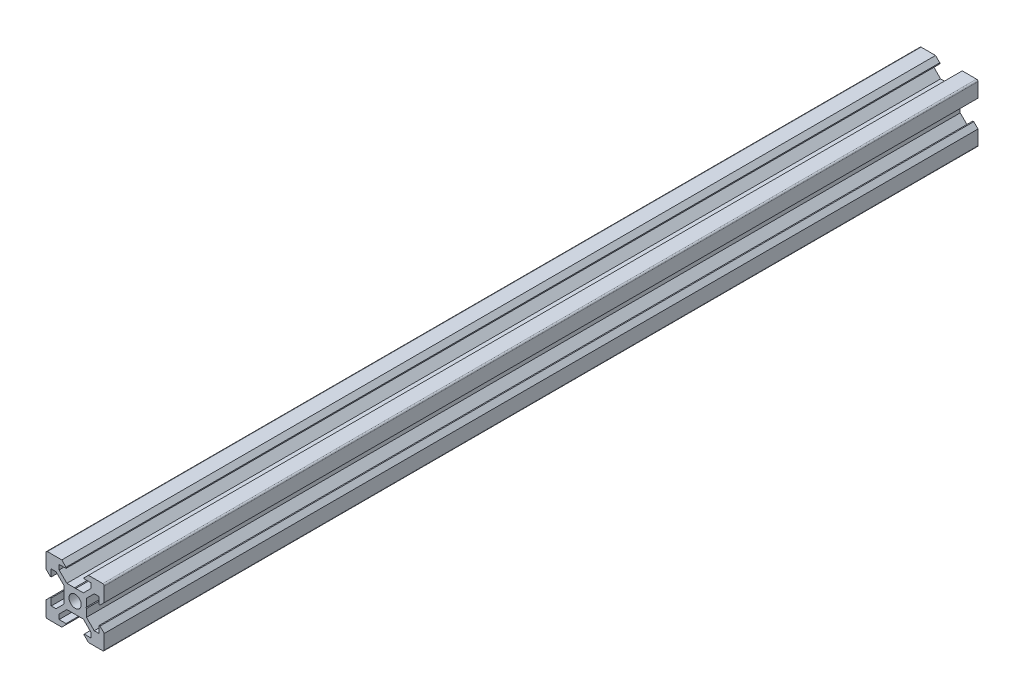
SolidWorks part; units mm, degrees
material "6061-T6 (SS)"
ref_plane "Front Plane" through (0, 0, 0) normal (0, 0, 1) x (1, 0, 0)
ref_plane "Top Plane" through (0, 0, 0) normal (0, 1, 0) x (1, 0, 0)
ref_plane "Right Plane" through (0, 0, 0) normal (1, 0, 0) x (0, 0, -1)
sketch "Sketch1" plane through (0, 0, 0) normal (0, 0, 1) x (1, 0, 0)
  line L1 (9.5, -10) -> (-9.5, -10)
  line L2 (10, -9.5) -> (10, 9.5)
  line L3 (9.5, 10) -> (-9.5, 10)
  line L4 (-10, -9.5) -> (-10, 9.5)
  line L5 (10, -10) -> (-10, 10) construction
  line L6 (10, 10) -> (-10, -10) construction
  circle A0 centre (0, 0) radius 2.1
  arc A1 (-9.5, 10) -> (-10, 9.5) centre (-9.5, 9.5) ccw
  arc A2 (10, 9.5) -> (9.5, 10) centre (9.5, 9.5) ccw
  arc A3 (9.5, -10) -> (10, -9.5) centre (9.5, -9.5) ccw
  arc A4 (-9.5, -10) -> (-10, -9.5) centre (-9.5, -9.5) cw
  point P0 (0, 0)
  line B0 (0, 0) -> (0, 10) construction
  line B1 (0, 3.69) -> (-0.21, 3.9)
  line B2 (-0.21, 3.9) -> (-2.8393, 3.9)
  line B3 (-2.8393, 3.9) -> (-5.5, 6.5607)
  line B4 (-5.5, 6.5607) -> (-5.5, 8.2)
  line B5 (-5.5, 8.2) -> (-3.125, 8.2)
  line B6 (-3.125, 8.2) -> (-3.125, 8.545)
  line B7 (-3.125, 8.545) -> (-4.58, 10)
  line B8 (-4.58, 10) -> (4.58, 10)
  line B9 (0, 0) -> (-5.9132, 5.9132) construction
  line B10 (3.125, 8.545) -> (4.58, 10)
  line B11 (3.125, 8.2) -> (3.125, 8.545)
  line B12 (5.5, 8.2) -> (3.125, 8.2)
  line B13 (5.5, 6.5607) -> (5.5, 8.2)
  line B14 (2.8393, 3.9) -> (5.5, 6.5607)
  line B15 (0.21, 3.9) -> (2.8393, 3.9)
  line B16 (0, 3.69) -> (0.21, 3.9)
  line B17 (0, 0) -> (-10, 0) construction
  line B18 (-3.69, 0) -> (-3.9, -0.21)
  line B19 (-3.9, -0.21) -> (-3.9, -2.8393)
  line B20 (-3.9, -2.8393) -> (-6.5607, -5.5)
  line B21 (-6.5607, -5.5) -> (-8.2, -5.5)
  line B22 (-8.2, -5.5) -> (-8.2, -3.125)
  line B23 (-8.2, -3.125) -> (-8.545, -3.125)
  line B24 (-8.545, -3.125) -> (-10, -4.58)
  line B25 (-10, -4.58) -> (-10, 4.58)
  line B26 (0, 0) -> (-5.9132, -5.9132) construction
  line B27 (-8.545, 3.125) -> (-10, 4.58)
  line B28 (-8.2, 3.125) -> (-8.545, 3.125)
  line B29 (-8.2, 5.5) -> (-8.2, 3.125)
  line B30 (-6.5607, 5.5) -> (-8.2, 5.5)
  line B31 (-3.9, 2.8393) -> (-6.5607, 5.5)
  line B32 (-3.9, 0.21) -> (-3.9, 2.8393)
  line B33 (-3.69, 0) -> (-3.9, 0.21)
  line B34 (0, 0) -> (0, -10) construction
  line B35 (0, -3.69) -> (0.21, -3.9)
  line B36 (0.21, -3.9) -> (2.8393, -3.9)
  line B37 (2.8393, -3.9) -> (5.5, -6.5607)
  line B38 (5.5, -6.5607) -> (5.5, -8.2)
  line B39 (5.5, -8.2) -> (3.125, -8.2)
  line B40 (3.125, -8.2) -> (3.125, -8.545)
  line B41 (3.125, -8.545) -> (4.58, -10)
  line B42 (4.58, -10) -> (-4.58, -10)
  line B43 (0, 0) -> (5.9132, -5.9132) construction
  line B44 (-3.125, -8.545) -> (-4.58, -10)
  line B45 (-3.125, -8.2) -> (-3.125, -8.545)
  line B46 (-5.5, -8.2) -> (-3.125, -8.2)
  line B47 (-5.5, -6.5607) -> (-5.5, -8.2)
  line B48 (-2.8393, -3.9) -> (-5.5, -6.5607)
  line B49 (-0.21, -3.9) -> (-2.8393, -3.9)
  line B50 (0, -3.69) -> (-0.21, -3.9)
  line B51 (0, 0) -> (10, 0) construction
  line B52 (3.69, 0) -> (3.9, 0.21)
  line B53 (3.9, 0.21) -> (3.9, 2.8393)
  line B54 (3.9, 2.8393) -> (6.5607, 5.5)
  line B55 (6.5607, 5.5) -> (8.2, 5.5)
  line B56 (8.2, 5.5) -> (8.2, 3.125)
  line B57 (8.2, 3.125) -> (8.545, 3.125)
  line B58 (8.545, 3.125) -> (10, 4.58)
  line B59 (10, 4.58) -> (10, -4.58)
  line B60 (0, 0) -> (5.9132, 5.9132) construction
  line B61 (8.545, -3.125) -> (10, -4.58)
  line B62 (8.2, -3.125) -> (8.545, -3.125)
  line B63 (8.2, -5.5) -> (8.2, -3.125)
  line B64 (6.5607, -5.5) -> (8.2, -5.5)
  line B65 (3.9, -2.8393) -> (6.5607, -5.5)
  line B66 (3.9, -0.21) -> (3.9, -2.8393)
  line B67 (3.69, 0) -> (3.9, -0.21)
  dimension "D1" = 4.2
  dimension "D3" = 0.5
  dimension "D2" = 20
sketch_block_instance "V Slot 1-4"
sketch_block "V Slot 1" parameters "D1"=10, "D2"=11, "D3"=4.3, "D4"=1.8, "D5"=0.21, "D6"=45, "D7"=9.16, "D8"=1.5, "D9"=6.25
sketch_block_instance "V Slot 1-5"
sketch_block_instance "V Slot 1-6"
sketch_block_instance "V Slot 1-7"
extrude "Boss-Extrude1" add sketch "Sketch1" along normal mid plane 300 contours B67 B52 B53 B54 B55 B56 B57 B58 L2 A2 L3 B10 B11 B12 B13 B14 B15 B16 B1 B2 B3 B4 B5 B6 B7 A1 L4 B27 B28 B29 B30 B31 B32 B33 B18 B19 B20 B21 B22 B23 B24 A4 L1 B44 B45 B46 B47 B48 B49 region at (7.04, -9.7172, 0)
